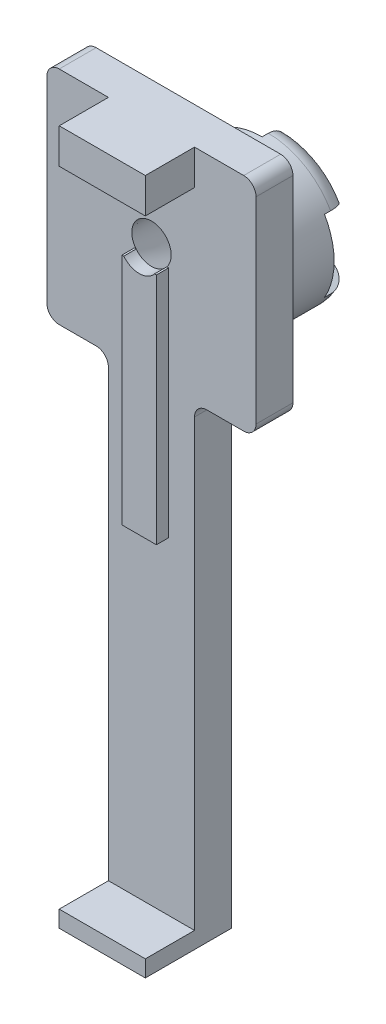
SolidWorks part; units mm, degrees
ref_plane "Front Plane" through (0, 0, 0) normal (0, 0, 1) x (1, 0, 0)
ref_plane "Top Plane" through (0, 0, 0) normal (0, 1, 0) x (1, 0, 0)
ref_plane "Right Plane" through (0, 0, 0) normal (1, 0, 0) x (0, 0, -1)
sketch "Sketch1" plane through (0, 0, 0) normal (0, 0, 1) x (1, 0, 0)
  line L7 (3.5, -18.4549) -> (-3.5, -18.4549)
  line L8 (3.5, -18.4549) -> (3.5, 38.0451)
  line L9 (3.5, 38.0451) -> (-3.5, 38.0451)
  line L10 (-3.5, -18.4549) -> (-3.5, 38.0451)
  line L11 (3.5, -18.4549) -> (-3.5, 38.0451) construction
  line L12 (3.5, 38.0451) -> (-3.5, -18.4549) construction
  point P6 (0, 9.7951)
  dimension "D3" = 56.5
  dimension "D4" = 7
extrude "Boss-Extrude1" add sketch "Sketch1" along normal blind 3 contours L10 L7 L8 L9 region at (0, 9.7951, 0)
sketch "Sketch2" plane through (0, 0, 3) normal (0, 0, 1) x (1, 0, 0)
  line L0 (3.5, -18.4549) -> (-3.5, -18.4549) construction
  line L1 (0, 9.4951) -> (0, -18.4549) construction
  line L16 (-1.4, 9.4951) -> (1.4, 9.4951)
  line L17 (-1.4, 28.4951) -> (-1.4, 9.4951)
  line L18 (1.4, 28.4951) -> (-1.4, 28.4951)
  line L19 (1.4, 9.4951) -> (1.4, 28.4951)
  point P0 (0, 9.4951)
  dimension "D1" = 27.95
  dimension "D2" = 19
  dimension "D3" = 2.8
extrude "Boss-Extrude2" add sketch "Sketch2" along normal blind 1
sketch "Sketch3" plane through (0, 0, 3) normal (0, 0, 1) x (1, 0, 0)
  line L0 (3.5, -18.4549) -> (3.5, 38.0451) construction
  line L1 (-3.5, 38.0451) -> (3.5, 38.0451)
  line L2 (-3.5, 38.0451) -> (-3.5, 35.1951)
  line L3 (-3.5, 35.1951) -> (3.5, 35.1951)
  line L4 (3.5, 38.0451) -> (3.5, 35.1951)
  line L5 (-3.5, -18.4549) -> (-3.5, 38.0451) construction
  line L6 (3.5, -18.4549) -> (-3.5, -18.4549)
  line L7 (3.5, -18.4549) -> (3.5, -17.1049)
  line L8 (3.5, -17.1049) -> (-3.5, -17.1049)
  line L9 (-3.5, -18.4549) -> (-3.5, -17.1049)
  dimension "D1" = 2.85
  dimension "D2" = 1.35
extrude "Boss-Extrude3" add sketch "Sketch3" along normal blind 4
sketch "Sketch4" plane through (-3.5, 0, 0) normal (-1, 0, 0) x (0, 0, 1)
  line L0 (3, -17.1049) -> (3, 35.1951) construction
  line L1 (0, 38.0451) -> (3, 38.0451)
  line L2 (0, 38.0451) -> (0, 20.0451)
  line L3 (0, 20.0451) -> (3, 20.0451)
  line L4 (3, 38.0451) -> (3, 20.0451)
  dimension "D1" = 18
extrude "Boss-Extrude4" add sketch "Sketch4" along normal blind 5
sketch "Sketch5" plane through (3.5, 0, 0) normal (1, 0, 0) x (0, 0, -1)
  line L4 (0, 38.0451) -> (-3, 38.0451)
  line L5 (-3, 38.0451) -> (-3, 20.0451)
  line L6 (-3, 20.0451) -> (0, 20.0451)
  line L7 (0, 20.0451) -> (0, 38.0451)
  line L8 (0, 38.0451) -> (-3, 38.0451)
  line L9 (-3, 38.0451) -> (-3, 20.0451)
  line L10 (-3, 20.0451) -> (0, 20.0451)
  line L11 (0, 20.0451) -> (0, 38.0451)
  dimension "D1" = 0
extrude "Boss-Extrude5" add sketch "Sketch5" along normal blind 5
sketch "Sketch7" plane through (0, 0, 3) normal (0, 0, 1) x (1, 0, 0)
  line L0 (-1.4, 9.4951) -> (1.4, 9.4951) construction
  circle A0 centre (0, 29.4951) radius 1.6
  dimension "D1" = 3.2
  dimension "D2" = 20
sketch "Sketch9" plane through (0, 0, 0) normal (0, 0, -1) x (-1, 0, 0)
  line L0 (0, 38.0451) -> (0, -18.4549) construction
  line L1 (-8.5, 38.0451) -> (8.5, 38.0451) construction
  line L2 (-3.5, -18.4549) -> (3.5, -18.4549) construction
  circle A0 centre (0, 26.6701) radius 5.85
  dimension "D1" = 11.7
  dimension "D2" = 11.375
extrude "Boss-Extrude7" add sketch "Sketch9" along normal blind 8
sketch "Sketch10" plane through (0, 0, -8) normal (0, 0, -1) x (-1, 0, 0)
  line L0 (0, 32.5201) -> (0, 20.8201)
  line L1 (-5.0662, 29.5951) -> (5.0662, 23.7451)
  line L2 (5.0662, 29.5951) -> (-5.0662, 23.7451)
  circle A3 centre (0, 26.6701) radius 5.85
  circle A4 centre (0, 26.6701) radius 5.85 construction
  circle M5 centre (0, 26.6701) radius 5.85
  dimension "D1" = 60
  dimension "D2" = 60
fillet "Fillet1" radius 1.5 1 edges at (-5.85, 26.6701, -8)
fillet "Fillet2" radius 1 6 edges at (-3.5, 20.0451, 1.5) (-8.5, 20.0451, 1.5) (-8.5, 38.0451, 1.5) (8.5, 38.0451, 1.5) (8.5, 20.0451, 1.5) (3.5, 20.0451, 1.5)
sketch "Sketch11" plane through (0, 0, -8) normal (0, 0, -1) x (-1, 0, 0)
  circle A0 centre (0, 26.6701) radius 3.4369
ref_plane "Plane1" through (0, 0, 0) normal (1, 0, 0) x (0, 0, -1)
loft "Cut-Loft6" cut profiles "Sketch11", "Sketch7" connector at (-0.0086, 30.107, -8) connector at (0, 31.0951, 3)
extrude "Cut-Extrude5" cut sketch "Sketch10" against normal blind 2 contours L2 L1 M5 | L2 L0 M5 | L1 L0 M5 region at (-1.8621, 29.8954, -8) region at (-1.8621, 23.4448, -8) region at (3.7242, 26.6701, -8)
sketch "Sketch14" plane through (0, 0, 3) normal (0, 0, 1) x (1, 0, 0)
  circle A0 centre (0, 29.4951) radius 1.6
  circle A1 centre (0, 29.4951) radius 1.6 construction
extrude "Cut-Extrude6" cut sketch "Sketch14" along normal blind 3
